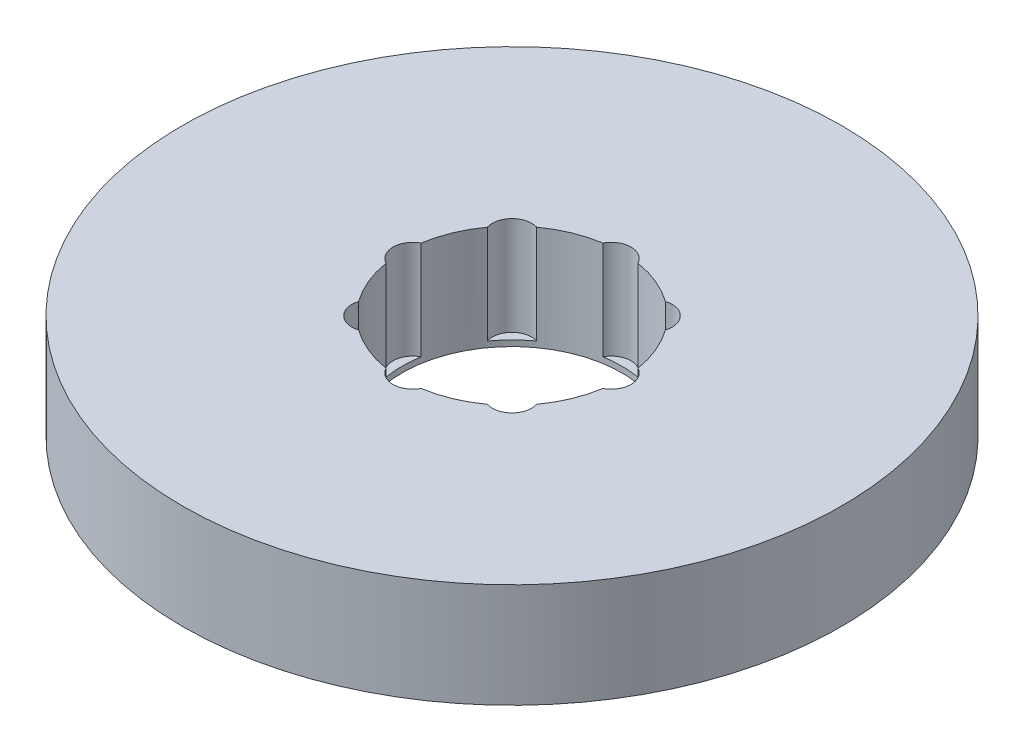
SolidWorks part; units mm, degrees
ref_plane "Front Plane" through (0, 0, 0) normal (0, 0, 1) x (1, 0, 0)
ref_plane "Top Plane" through (0, 0, 0) normal (0, 1, 0) x (1, 0, 0)
ref_plane "Right Plane" through (0, 0, 0) normal (1, 0, 0) x (0, 0, -1)
sketch "Sketch1" plane through (0, 0, 0) normal (0, 1, 0) x (1, 0, 0)
  circle A0 centre (0, 0) radius 60
  dimension "FLANGE_OD" = 120
extrude "Boss-Extrude1" add sketch "Sketch1" along normal blind 19
sketch "Sketch2" plane through (0, 0, 0) normal (0, 1, 0) x (1, 0, 0)
  circle A0 centre (0, 0) radius 20
  dimension "BORE_D" = 40
extrude "Cut-Extrude1" cut sketch "Sketch2" along normal through all
sketch "Sketch3" plane through (0, 19, 0) normal (0, 1, 0) x (1, 0, 0)
  circle A0 centre (0, 0) radius 18.0656 construction
  circle A1 centre (-18.0656, 0) radius 3.6005
  dimension "BOLT_D" = 7.2009
  dimension "BOLT_PCD" = 36.1312
extrude "Cut-Extrude2" cut sketch "Sketch3" against normal blind 17.9374
pattern_circular "CirPattern1" count 8 over 360 about axis through (0, 0, 0) along (0, 1, 0) of "Cut-Extrude2"
